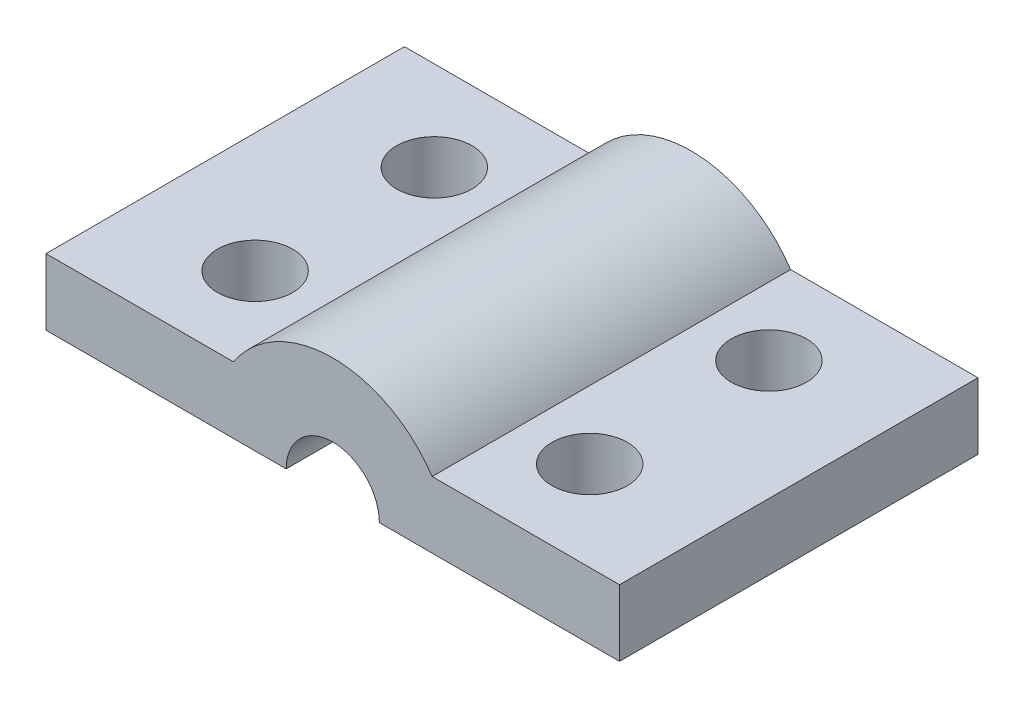
SolidWorks part; units mm, degrees
ref_plane "Front Plane" through (0, 0, 0) normal (0, 0, 1) x (1, 0, 0)
ref_plane "Top Plane" through (0, 0, 0) normal (0, 1, 0) x (1, 0, 0)
ref_plane "Right Plane" through (0, 0, 0) normal (1, 0, 0) x (0, 0, -1)
sketch "Sketch1" plane through (0, 0, 0) normal (0, 0, 1) x (1, 0, 0)
  line L0 (-5, 0) -> (-12, 0)
  line L1 (-12, 0) -> (-12, 2.7775)
  line L2 (-12, 2.7775) -> (-4.1576, 2.7775)
  line L3 (-5, 0) -> (-1.95, 0)
  line L4 (0, 0) -> (0, 5) construction
  line L5 (5, 0) -> (1.95, 0)
  line L6 (12, 2.7775) -> (4.1576, 2.7775)
  line L7 (12, 0) -> (12, 2.7775)
  line L8 (5, 0) -> (12, 0)
  circle A0 centre (0, 0) radius 5
  circle A1 centre (0, 0) radius 1.95
  dimension "D3" = 3.9
  dimension "D4" = 10
  dimension "D1" = 7
  dimension "D2" = 2.7775
extrude "Boss-Extrude1" add sketch "Sketch1" along normal blind 7.5 contours A0 L2 L1 L0 | A1 L4 A0 L3 | L4 A1 L5 A0 | A0 L8 L7 L6 region at (-2.3543, 2.3543, 0) region at (-8.3605, 1.4151, 0) region at (8.3605, 1.4151, 0) region at (2.3543, 2.3543, 0)
sketch "Sketch2" plane through (0, 2.7775, 0) normal (0, 1, 0) x (1, 0, 0)
  line L0 (-12, -7.5) -> (-12, 0) construction
  circle A0 centre (-7, -3.75) radius 1.575
  point P5 (-12, -3.75)
  dimension "D1" = 3.15
  dimension "D2" = 7
extrude "Cut-Extrude1" cut sketch "Sketch2" against normal through all both and the other way through all
mirror "Mirror1" about plane through (0, 0, 0) normal (1, 0, 0) of "Cut-Extrude1"
mirror "Mirror2" about plane through (0, 0, 0) normal (0, 0, 1) of "Mirror1", "Cut-Extrude1", "Boss-Extrude1"
